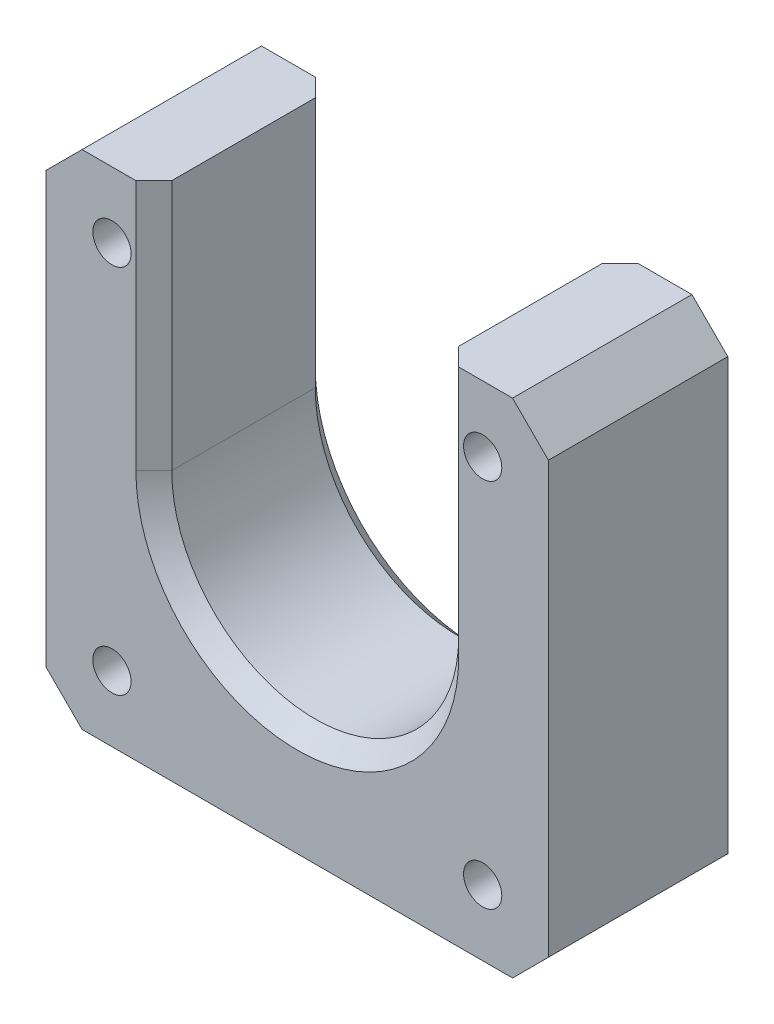
SolidWorks part; units mm, degrees
ref_plane "Front Plane" through (0, 0, 0) normal (0, 0, 1) x (1, 0, 0)
ref_plane "Top Plane" through (0, 0, 0) normal (0, 1, 0) x (1, 0, 0)
ref_plane "Right Plane" through (0, 0, 0) normal (1, 0, 0) x (0, 0, -1)
sketch "Sketch1" plane through (0, 0, 0) normal (0, 0, 1) x (1, 0, 0)
  line L1 (-21, 21) -> (21, 21)
  line L2 (-21, 21) -> (-21, -21)
  line L3 (-21, -21) -> (21, -21)
  line L4 (21, 21) -> (21, -21)
extrude "Boss-Extrude1" add sketch "Sketch1" along normal blind 15
sketch "Sketch2" plane through (0, 0, 15) normal (0, 0, 1) x (1, 0, 0)
  line L0 (-12, 0) -> (-12, 21)
  line L1 (-12, 21) -> (12, 21)
  line L2 (12, 21) -> (12, 0)
  circle A0 centre (-15.5, 15.5) radius 1.6
  circle A1 centre (15.5, -15.5) radius 1.6
  circle A3 centre (15.5, 15.5) radius 1.6
  circle A4 centre (-15.5, -15.5) radius 1.6
  arc A5 (-12, 0) -> (12, 0) centre (0, 0) ccw
extrude "Cut-Extrude1" cut sketch "Sketch2" against normal blind 30
fillet "Chamfer1" radius 3 1 edges at (-21, 21, 7.5) type face fillet profile chamfer first side face at (-16.5, 21, 7.5) second side face at (-21, 0, 7.5)
fillet "Chamfer2" radius 3 1 edges at (21, 21, 7.5) type face fillet profile chamfer first side face at (16.5, 21, 7.5) second side face at (21, 0, 7.5)
fillet "Chamfer3" radius 3 1 edges at (21, -21, 7.5) type face fillet profile chamfer first side face at (21, -1.5, 7.5) second side face at (0, -21, 7.5)
fillet "Chamfer4" radius 3 1 edges at (-21, -21, 7.5) type face fillet profile chamfer first side face at (-1.5, -21, 7.5) second side face at (-21, -1.5, 7.5)
chamfer "Chamfer6" distance 1.5 angle 45 6 edges at (-12, 10.5, 0) (12, 10.5, 0) (0, -12, 0) (-12, 10.5, 15) (12, 10.5, 15) (0, -12, 15)
